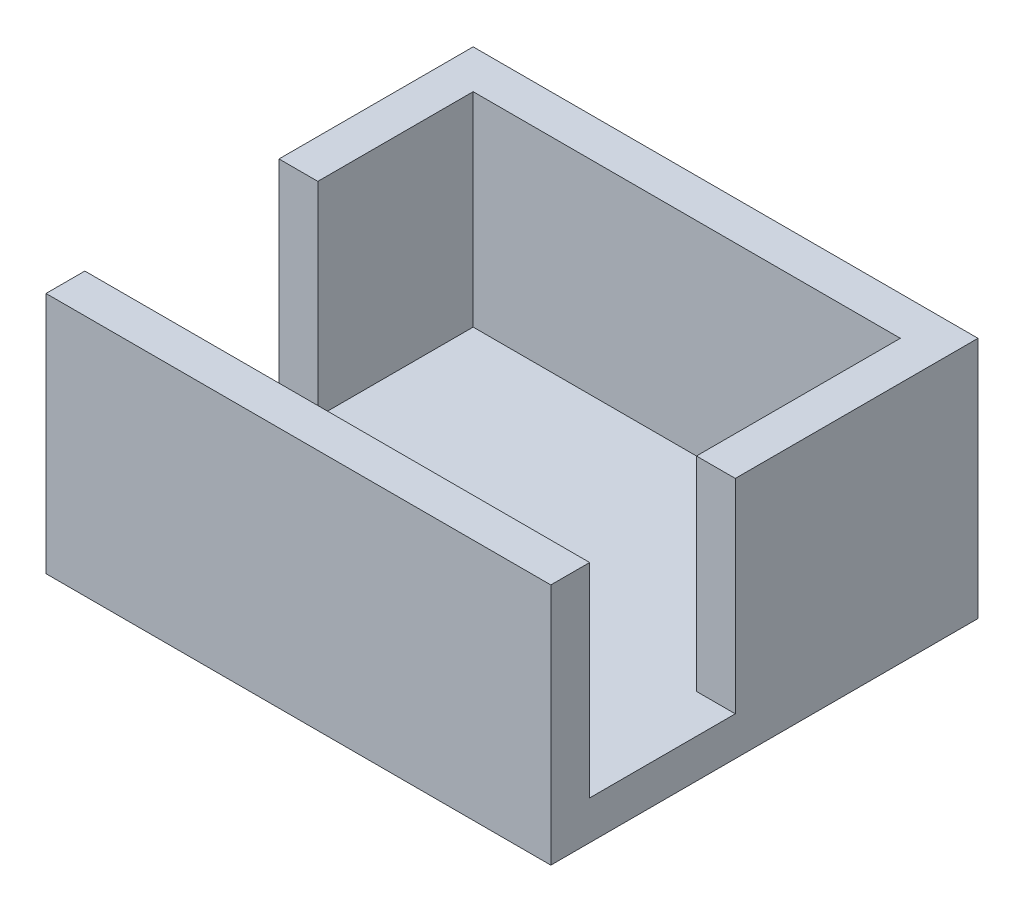
SolidWorks part; units mm, degrees
ref_plane "Front Plane" through (0, 0, 0) normal (0, 0, 1) x (1, 0, 0)
ref_plane "Top Plane" through (0, 0, 0) normal (0, 1, 0) x (1, 0, 0)
ref_plane "Right Plane" through (0, 0, 0) normal (1, 0, 0) x (0, 0, -1)
sketch "Sketch1" plane through (0, 0, 0) normal (0, 1, 0) x (1, 0, 0)
  line L0 (-2, 20) -> (24, 20)
  line L1 (0, 0) -> (22, 0)
  line L2 (0, 0) -> (0, 18)
  line L3 (0, 18) -> (22, 18)
  line L4 (22, 0) -> (22, 18)
  line L5 (24, -2) -> (24, 20)
  line L6 (-2, -2) -> (24, -2)
  line L7 (-2, -2) -> (-2, 20)
  dimension "D1" = 22
  dimension "D2" = 18
  dimension "D3" = 2
extrude "Boss-Extrude1" add sketch "Sketch1" along normal blind 2 contours L1 L4 L3 L2 | L7 L6 L5 L0 L4 L1 L2 L3 region at (11, 0, -19.6594) region at (11, 0, -9)
extrude "Boss-Extrude2" add sketch "Sketch1<3>" along normal blind 12.5
sketch "Sketch1<3>" plane through (0, 0, 0) normal (0, 1, 0) x (1, 0, 0) same geometry as "Sketch1"
sketch "Sketch2" plane through (0, 12.5, 0) normal (0, 1, 0) x (1, 0, 0)
  line L0 (-2, 20) -> (-2, -2) construction
  line L1 (0, 0) -> (-2, 0)
  line L2 (0, 0) -> (0, 10)
  line L3 (0, 10) -> (-2, 10)
  line L4 (-2, 0) -> (-2, 10)
  line L5 (24, -2) -> (24, 20) construction
  line L6 (22, 0) -> (24, 0)
  line L7 (22, 0) -> (22, 7.5)
  line L8 (22, 7.5) -> (24, 7.5)
  line L9 (24, 0) -> (24, 7.5)
  dimension "D1" = 7.5
  dimension "D2" = 10
extrude "Cut-Extrude1" cut sketch "Sketch2" against normal up to surface (10.5 mm away) up to face at (11, 2, -9)
